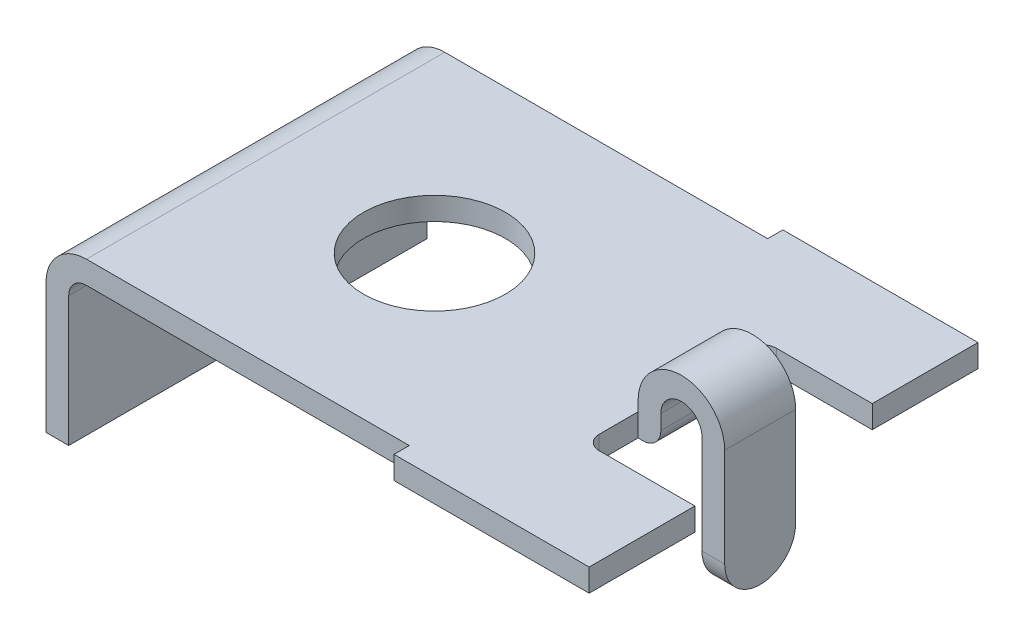
SolidWorks part; units mm, degrees
material "Chrome Stainless Steel"
ref_plane "Front Plane" through (0, 0, 0) normal (0, 0, 1) x (1, 0, 0)
ref_plane "Top Plane" through (0, 0, 0) normal (0, 1, 0) x (1, 0, 0)
ref_plane "Right Plane" through (0, 0, 0) normal (1, 0, 0) x (0, 0, -1)
ref_axis "X-axis" through (-88.99, 0, 0) along (1, 0, 0)
ref_axis "Y-axis" through (0, -55, 0) along (0, 1, 0)
ref_axis "Z-axis" through (0, 0, 55) along (0, 0, -1)
sketch "Sketch1" plane through (0, 0, 0) normal (0, 0, 1) x (1, 0, 0)
  line L0 (0, 0) -> (0, 6.096)
  line L1 (0, 6.096) -> (19.9898, 6.096)
  dimension "D1" = 19.9898
  dimension "D2" = 6.096
extrude "Extrude-Thin1" add sketch "Sketch1" along normal mid plane 12.827 thin thin type one direction wall 0.8128
sketch "Sketch2" plane through (0, 0, 0) normal (0, 0, 1) x (1, 0, 0)
  line L0 (1.4478, 5.2832) -> (19.9898, 5.2832) construction
  line L1 (19.9898, 6.096) -> (13.0048, 6.096)
  line L2 (19.9898, 6.096) -> (19.9898, 5.2832)
  line L3 (19.9898, 5.2832) -> (13.0048, 5.2832)
  line L4 (13.0048, 6.096) -> (13.0048, 5.2832)
  dimension "D1" = 6.985
extrude "Boss-Extrude1" add sketch "Sketch2" along normal mid plane 13.9192
sketch "Sketch3" plane through (0, 6.096, 0) normal (0, 1, 0) x (1, 0, 0)
  line L0 (19.9898, -6.9596) -> (19.9898, 6.9596) construction
  line L1 (19.9898, -3.175) -> (16.0528, -3.175)
  line L2 (19.9898, -3.175) -> (19.9898, 3.175)
  line L3 (19.9898, 3.175) -> (16.0528, 3.175)
  line L4 (16.0528, -3.175) -> (16.0528, 3.175)
  point P6 (16.0528, 0)
  point P7 (19.9898, 0)
  point P8 (19.9898, 0)
  dimension "D1" = 6.35
  dimension "D2" = 3.937
extrude "Cut-Extrude1" cut sketch "Sketch3" against normal through all
sketch "Sketch4" plane through (0, 0, 0) normal (0, 0, 1) x (1, 0, 0)
  line L0 (16.0528, 5.2832) -> (16.0528, 6.4516)
  line L1 (19.1516, 6.4516) -> (19.1516, 1.651)
  line L2 (19.9898, 6.096) -> (13.0048, 6.096) construction
  arc A0 (16.0528, 6.4516) -> (19.1516, 6.4516) centre (17.6022, 6.4516) cw
  point P8 (17.6022, 8.001)
  point P9 (19.1516, 4.3423)
  point P10 (16.0528, 5.2832)
  dimension "D1" = 3.0988
  dimension "D2" = 1.905
  dimension "D3" = 6.35
extrude "Extrude-Thin2" add sketch "Sketch4" along normal mid plane 2.54 thin thin type one direction wall 0.8128
fillet "Fillet1" 2 edges at (18.7452, 1.651, 1.27) (18.7452, 1.651, -1.27) type full round first side face at (17.43, 5.3396, 1.27) second side face at (17.43, 5.3396, -1.27) middle face at (18.7452, 1.651, 0)
fillet "Fillet2" radius 0.635 1 edges at (16.8656, 5.2832, 0)
sketch "Sketch5" plane through (0, 6.096, 0) normal (0, 1, 0) x (1, 0, 0)
  line L0 (0, -6.4135) -> (0, 6.4135) construction
  circle A0 centre (7.493, 0) radius 2.54
  point P4 (0, 0)
  point P5 (0, 0)
  dimension "D1" = 5.08
  dimension "D2" = 4.953
extrude "Cut-Extrude2" cut sketch "Sketch5" against normal through all
fillet "Fillet3" radius 0.508 2 edges at (16.0528, 5.6896, 3.175) (16.0528, 5.6896, -3.175)
